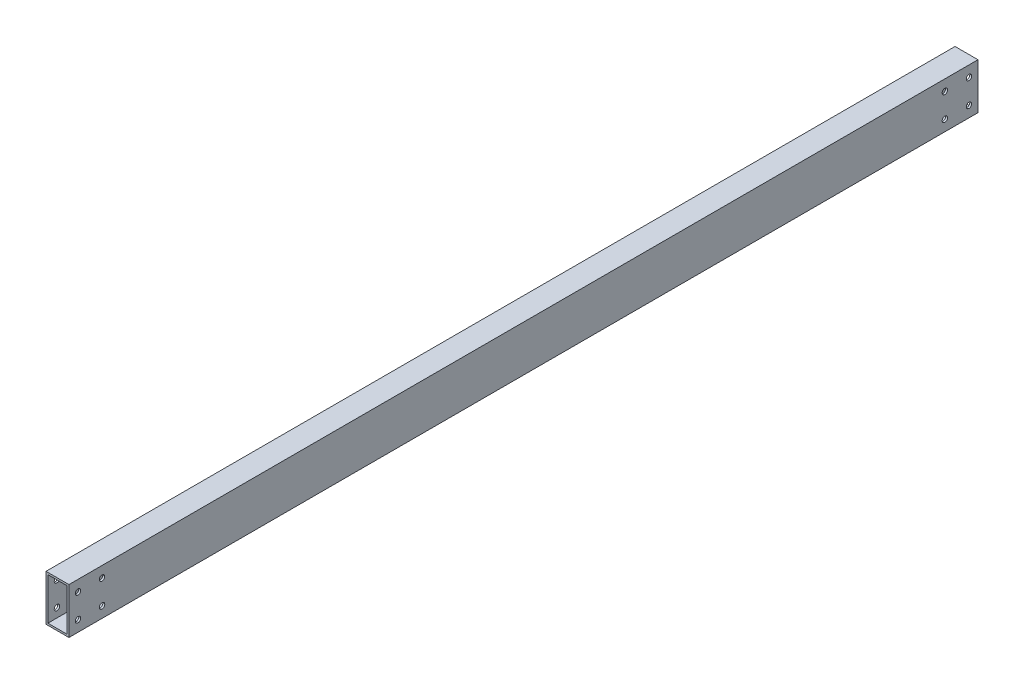
SolidWorks part; units mm, degrees
material "6063-T6"
ref_plane "Front Plane" through (0, 0, 0) normal (0, 0, 1) x (1, 0, 0)
ref_plane "Top Plane" through (0, 0, 0) normal (0, 1, 0) x (1, 0, 0)
ref_plane "Right Plane" through (0, 0, 0) normal (1, 0, 0) x (0, 0, -1)
sketch "Sketch1" plane through (0, 0, 0) normal (0, 0, 1) x (1, 0, 0)
  line L1 (-19.05, 38.1) -> (19.05, 38.1)
  line L2 (-19.05, 38.1) -> (-19.05, -38.1)
  line L3 (-19.05, -38.1) -> (19.05, -38.1)
  line L4 (19.05, 38.1) -> (19.05, -38.1)
  line L5 (-19.05, 38.1) -> (19.05, -38.1) construction
  line L6 (-19.05, -38.1) -> (19.05, 38.1) construction
  point P0 (0, 0)
  dimension "D1" = 38.1
  dimension "D2" = 76.2
extrude "Extrude-Thin1" add sketch "Sketch1" along normal mid plane 1510 thin thin type one direction reverse wall 3.175
hole_wizard "M8 Clearance Hole2" positions "Sketch5" profile "Sketch6" hole size "M8" standard "ANSI Metric" end condition up to next
sketch "Sketch5" plane through (19.05, 0, 0) normal (1, 0, 0) x (0, 0, -1)
  line L0 (-740, 20) -> (-740, -20)
  line L2 (20.955, 0) -> (-20.955, 0) construction
  line L3 (-755, -38.1) -> (-755, 38.1) construction
  line L4 (-740, 20) -> (-700, 20)
  line L5 (-700, 20) -> (-700, -20)
  line L6 (-700, -20) -> (-740, -20)
  point P0 (-740, 20)
  point P2 (-740, -20)
  point P9 (-740, 0)
  point P24 (-700, 20)
  point P27 (-700, -20)
  dimension "D1" = 40
  dimension "D2" = 15
sketch "Sketch6" plane through (19.05, 20, 740) normal (0, 1, 0) x (0, 0, -1)
  line L0 (0, 0) -> (0, 3.175)
  line L1 (0, 3.175) -> (4.5, 3.175)
  line L2 (4.5, 3.175) -> (4.5, 0)
  line L5 (4.5, 0) -> (0, 0)
  line L11 (0, -6.35) -> (0, 107.95) construction
  dimension "Thru Hole Dia." = 9
  dimension "Thru Hole Depth" = 3.175
hole_wizard "M8 Clearance Hole1" positions "Sketch7" profile "Sketch8" hole size "M8" standard "ANSI Metric" end condition up to next
sketch "Sketch7" plane through (-15.875, 0, 0) normal (1, 0, 0) x (0, 0, -1)
  point P0 (-740, 20)
  point P3 (-740, -20)
  point P6 (-700, 20)
  point P9 (-700, -20)
sketch "Sketch8" plane through (-15.875, 20, 740) normal (0, 1, 0) x (0, 0, -1)
  line L0 (0, 0) -> (0, 3.175)
  line L1 (0, 3.175) -> (4.5, 3.175)
  line L2 (4.5, 3.175) -> (4.5, 0)
  line L5 (4.5, 0) -> (0, 0)
  line L11 (0, -6.35) -> (0, 107.95) construction
  dimension "Thru Hole Dia." = 9
  dimension "Thru Hole Depth" = 3.175
mirror "Mirror1" about plane through (0, 0, 0) normal (0, 0, 1) of "M8 Clearance Hole2", "M8 Clearance Hole1"
